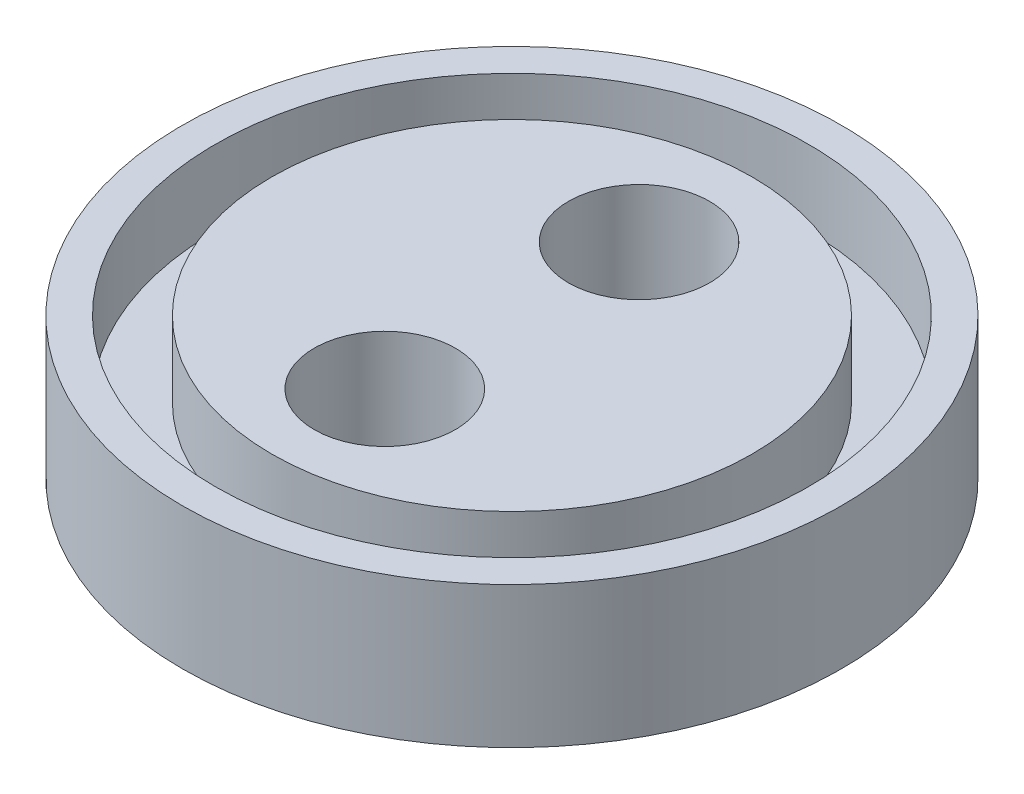
SolidWorks part; units mm, degrees
ref_plane "Front Plane" through (0, 0, 0) normal (0, 0, 1) x (1, 0, 0)
ref_plane "Top Plane" through (0, 0, 0) normal (0, 1, 0) x (1, 0, 0)
ref_plane "Right Plane" through (0, 0, 0) normal (1, 0, 0) x (0, 0, -1)
sketch "Sketch4" plane through (0, 0, 0) normal (0, 1, 0) x (1, 0, 0)
  line L0 (0, 0) -> (0, 13.5) construction
  line L1 (0, 0) -> (0, -13.5) construction
  circle A1 centre (0, 0) radius 17.5
  circle A2 centre (0, 6.75) radius 3.75
  circle A3 centre (0, -6.75) radius 3.75
  dimension "D1" = 13.5
  dimension "D2" = 35
  dimension "D4" = 7.5
  dimension "D5" = 7.5
  dimension "D3" = 13.5
extrude "LidBase" add sketch "Sketch4" along normal blind 7.5
sketch "Sketch5" plane through (0, 7.5, 0) normal (0, 1, 0) x (1, 0, 0)
  circle A0 centre (0, 0) radius 12.75
  circle A1 centre (0, 0) radius 15.75
  dimension "D1" = 31.5
  dimension "D2" = 25.5
extrude "LidGrooves" cut sketch "Sketch5" against normal blind 4
